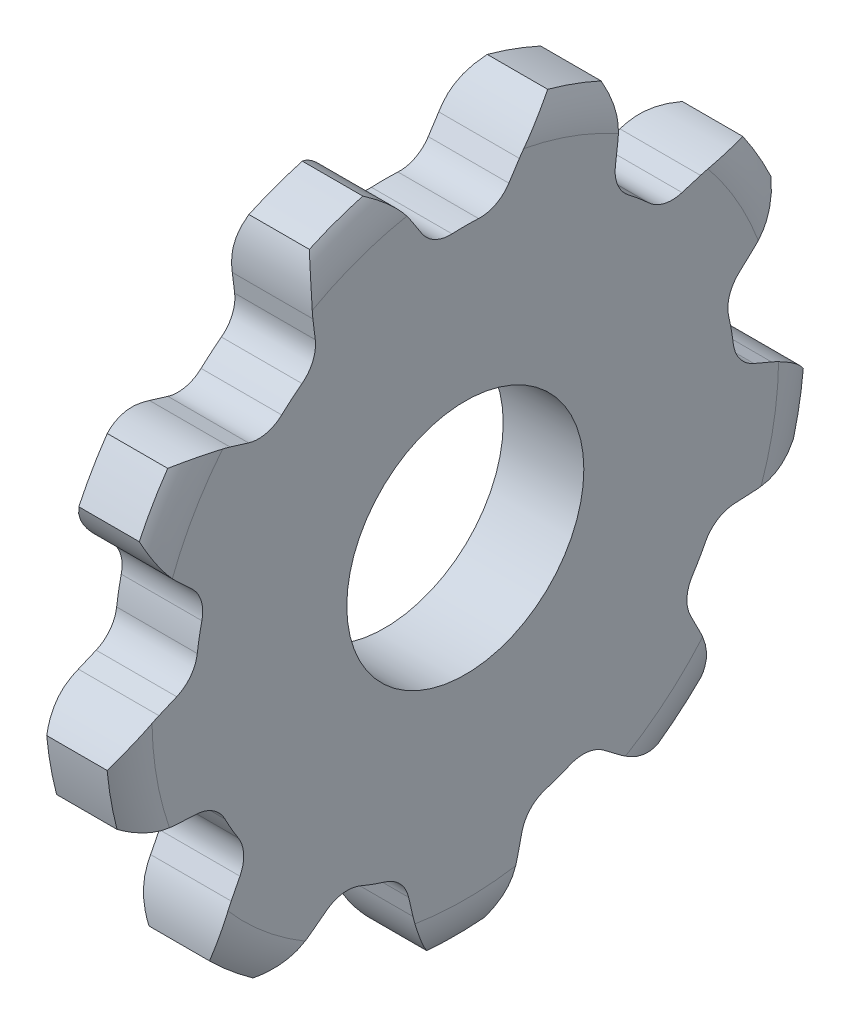
SolidWorks part; units mm, degrees
ref_plane "Plane1" through (0, 0, 0) normal (0, 0, 1) x (1, 0, 0)
ref_plane "Plane2" through (0, 0, 0) normal (0, 1, 0) x (1, 0, 0)
ref_plane "Plane3" through (0, 0, 0) normal (1, 0, 0) x (0, 0, -1)
sketch "Clipboard" plane through (0, 0, 0) normal (0, 1, 0) x (1, 0, 0)
  line L0 (0, 0) -> (22.6789, -3.592)
  line L1 (-15, 0) -> (100, 0) construction
  line L2 (0, 0) -> (-2.1039, 2.3779)
  line L3 (0, 0) -> (-11.863, 4.5341)
  line L4 (0, 0) -> (8.5297, 1.351)
  line L5 (0, 0) -> (-20.9428, -7.811)
  line L6 (0, 0) -> (-7.1589, -4.8301)
  line L7 (-2.1039, 2.3779) -> (2.7074, 24.206)
  line L8 (-76.2, 54.61) -> (-47.9044, 54.61)
  line L9 (-67.0794, 25.4907) -> (-62.6246, 26.5192)
  line L10 (-76.2, 71.12) -> (-42.6324, 71.12)
  circle A0 centre (0, 0) radius 7.9375
  circle A1 centre (0, 0) radius 25.4
  circle A2 centre (0, 0) radius 25.4
  dimension "Num_teeth" = 9
  dimension "Pitch_radius" = 33.5676
  dimension "H" = 4.572
  dimension "Thickness" = 8.636
sketch "BasProSke" plane through (0, 0, 0) normal (0, 1, 0) x (1, 0, 0)
  line L0 (-10, 0) -> (60, 0) construction
  line L1 (0, 0) -> (0, 33.5676)
  line L2 (0, 0) -> (8.636, 0)
  line L3 (8.636, 0) -> (8.636, 33.5676)
  line L4 (7.5565, 37.4538) -> (1.0795, 37.4538)
  arc A0 (0, 33.5676) -> (1.0795, 37.4538) centre (7.5349, 33.5676) cw
  arc A1 (8.636, 33.5676) -> (7.5565, 37.4538) centre (1.1011, 33.5676) ccw
  dimension "D1" = 7.5349
  dimension "Thickness" = 8.636
  dimension "Diameter" = 74.9076
revolve "Base-Revolve" add sketch "BasProSke" angle 360 about L0
sketch "TooCutSke" plane through (0, 0, 0) normal (1, 0, 0) x (0, 0, -1)
  line L0 (-4.6667, 30.5715) -> (-5.7922, 32.3047)
  line L1 (0, 0) -> (0, 107) construction
  line L2 (1.1481, 0) -> (1.1481, 288.74) construction
  line L3 (4.6667, 30.5715) -> (5.7922, 32.3047)
  line L5 (1.1481, 35.3206) -> (42.4634, 8.4901) construction
  arc A0 (1.4197, 28.9104) -> (-1.4197, 28.9104) centre (0, 0) ccw
  arc A1 (1.4197, 28.9104) -> (4.6667, 30.5715) centre (1.5991, 32.5636) ccw
  arc A2 (-1.4197, 28.9104) -> (-4.6667, 30.5715) centre (-1.5991, 32.5636) cw
  circle A3 centre (0, 0) radius 33.5676 construction
  circle A4 centre (1.1481, 33.548) radius 4.572 construction
  arc A5 (5.7922, 32.3047) -> (13.6084, 37.3886) centre (15.4208, 26.0518) cw
  arc A6 (-5.7922, 32.3047) -> (-13.6084, 37.3886) centre (-15.4208, 26.0518) ccw
  arc A7 (13.6084, 37.3886) -> (-13.6084, 37.3886) centre (0, 0) ccw
  dimension "Pitch_radius" = 33.5676
  dimension "R" = 3.6576
  dimension "Dr" = 28.9453
  dimension "H" = 4.572
  dimension "Ag" = 66
  dimension "L" = 2.0665
  dimension "Angle" = 40
extrude "ToothCut" cut sketch "TooCutSke" along normal through all
pattern_circular "TeethCuts" count 9 every 40 about axis through (-10, 0, 0) along (1, 0, 0) of "ToothCut"
sketch "HubNeaOneSke" plane through (0, 0, 0) normal (-1, 0, 0) x (0, 0, 1)
  circle A0 centre (0, 0) radius 25.4
  dimension "Diameter" = 50.8
extrude "HubNearOne" [suppressed] add sketch "HubNeaOneSke" along normal blind 13.7161
sketch "HubNeaBotSke" plane through (0, 0, 0) normal (-1, 0, 0) x (0, 0, 1)
  circle A0 centre (0, 0) radius 25.4
  dimension "Diameter" = 50.8
extrude "HubNearBoth" [suppressed] add sketch "HubNeaBotSke" along normal blind 6.858
ref_plane "FarPln" through (8.636, 0, 0) normal (1, 0, 0) x (0, 0, -1)
sketch "HubFarSke" plane through (8.636, 0, 0) normal (1, 0, 0) x (0, 0, -1)
  circle A0 centre (0, 0) radius 25.4
  dimension "Diameter" = 50.8
extrude "HubFar" [suppressed] add sketch "HubFarSke" along normal blind 6.858
sketch "BorSke" plane through (0, 0, 0) normal (1, 0, 0) x (0, 0, -1)
  circle A0 centre (0, 0) radius 12.7
  dimension "Diameter" = 25.4
extrude "Bore" cut sketch "BorSke" along normal mid plane 44.7041
sketch "KeySke" plane through (0, 0, 0) normal (1, 0, 0) x (0, 0, -1)
  line L0 (-3.175, 0) -> (-3.175, 15.5956)
  line L1 (-3.175, 15.5956) -> (3.175, 15.5956)
  line L2 (3.175, 15.5956) -> (3.175, 0)
  line L3 (0, 0) -> (0, 34) construction
  line L4 (-3.175, 0) -> (3.175, 0)
  dimension "Width" = 6.35
extrude "Keyway" [suppressed] cut sketch "KeySke" along normal mid plane 44.7041
pattern_circular "Keyway2" [suppressed] count 2 every 90 about axis through (-10, 0, 0) along (1, 0, 0)
equation "\"Num_teeth@Clipboard\" = int( \"Num_teeth@Clipboard\" )"
equation "\"Num_teeth@Clipboard\" = ((sgn( \"Num_teeth@Clipboard\" - 5.0)+1)*( \"Num_teeth@Clipboard\" - 5.0))/2 +5.0"
equation "' \"Num_teeth@Clipboard\" = ((sgn( \"Num_teeth@Clipboard\" - 200.0)-1)*( \"Num_teeth@Clipboard\" - 200.0))/-2 +200.0"
equation "\"OAL@Clipboard\" = \"Thickness@Clipboard\""
equation "\"Pitch_radius@Clipboard\" = ( \"Pitch@Clipboard\" / 2.0) / sin(3.14159265 / \"Num_teeth@Clipboard\" )"
equation "\"MHD@Clipboard\" =2.0 * ( \"Pitch_radius@Clipboard\" * 0.9985 -  \"H@Clipboard\" )"
equation "\"MHD@Clipboard\" = ((sgn( \"MHD@Clipboard\" - \"Hub_dia@Clipboard\" )-1)*( \"MHD@Clipboard\" - \"Hub_dia@Clipboard\" ))/-2+ \"Hub_dia@Clipboard\""
equation "\"OAL@Clipboard\" = ((sgn( \"OAL@Clipboard\" - \"Overall_len@Clipboard\" )+1)*( \"OAL@Clipboard\" - \"Overall_len@Clipboard\" ))/2 + \"Overall_len@Clipboard\" + 0.000002"
equation "\"Num_teeth@TeethCuts\" = int( \"Show_teeth@Clipboard\" ) + 1"
equation "\"Num_teeth@TeethCuts\" = ((sgn( \"Num_teeth@TeethCuts\" - \"Num_teeth@Clipboard\" )-1)*( \"Num_teeth@TeethCuts\" - \"Num_teeth@Clipboard\" ))/-2+ \"Num_teeth@Clipboard\""
equation "\"Num_teeth@TeethCuts\" = ((sgn( \"Num_teeth@TeethCuts\" - 2.0)+1)*( \"Num_teeth@TeethCuts\" - 2.0))/2 +2.0"
equation "\"Angle@TeethCuts\" = 360.0 / \"Num_teeth@Clipboard\""
equation "\"Pitch_radius@TooCutSke\" = \"Pitch_radius@Clipboard\""
equation "\"Cp@TooCutSke\" = 0.05 * \"Pitch@Clipboard\""
equation "\"Rt@TooCutSke\" = 0.5 * \"Pitch@Clipboard\""
equation "\"R@TooCutSke\"  = 0.8 * \"H@Clipboard\""
equation "\"Dr@TooCutSke\" = \"Pitch_radius@Clipboard\" * 0.9985 -  \"H@Clipboard\""
equation "\"Ag@TooCutSke\" =  2.0 * \"Ap@Clipboard\" + 360.0 / \"Num_teeth@Clipboard\""
equation "\"L@TooCutSke\" = 0.01 * \"Pitch@Clipboard\" * \"Num_teeth@Clipboard\""
equation "\"H@TooCutSke\" = \"H@Clipboard\""
equation "\"Angle@TooCutSke\" =  360.0 / \"Num_teeth@Clipboard\""
equation "\"Diameter@BasProSke\" = 2.0 * \"Pitch_radius@Clipboard\"  + 1.7 * \"H@Clipboard\""
equation "\"Thickness@BasProSke\"  = \"Thickness@Clipboard\""
equation "\"G1@BasProSke\" =  \"Thickness@Clipboard\" * 0.125"
equation "\"G2@BasProSke\" =   \"Thickness@Clipboard\" * 0.125"
equation "\"H1@BasProSke\" =  \"Diameter@BasProSke\" / 2.0 - \"Pitch_radius@Clipboard\""
equation "\"H2@BasProSke\" =  \"Diameter@BasProSke\" / 2.0 - \"Pitch_radius@Clipboard\""
equation "\"Diameter@HubNeaOneSke\" = \"MHD@Clipboard\""
equation "\"Length@HubNearOne\" = \"OAL@Clipboard\" - \"Thickness@BasProSke\""
equation "\"Diameter@HubNeaBotSke\" = \"MHD@Clipboard\""
equation "\"Length@HubNearBoth\" = ( \"OAL@Clipboard\" - \"Thickness@BasProSke\" ) / 2.0"
equation "\"Thickness@FarPln\" = \"Thickness@BasProSke\""
equation "\"Diameter@HubFarSke\" = \"MHD@Clipboard\""
equation "\"Length@HubFar\" = ( \"OAL@Clipboard\" - \"Thickness@BasProSke\" ) / 2.0"
equation "\"D1@Bore\" = \"OAL@Clipboard\" * 2.0"
equation "\"D1@Keyway\" = \"OAL@Clipboard\" * 2.0"
equation "\"Offset@KeySke\" = \"T_dim@Clipboard\" - \"Diameter@BorSke\" / 2.0"
